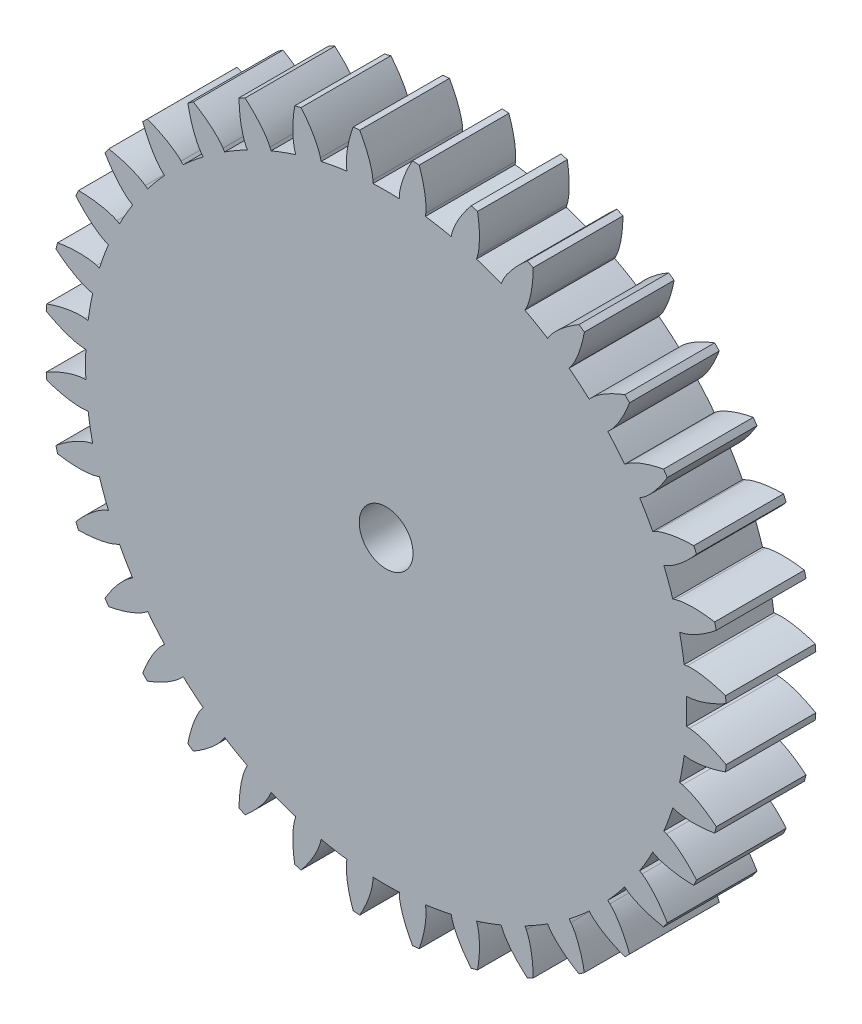
SolidWorks part; units mm, degrees
ref_plane "前视基准面" through (0, 0, 0) normal (0, 0, 1) x (1, 0, 0)
ref_plane "上视基准面" through (0, 0, 0) normal (0, 1, 0) x (1, 0, 0)
ref_plane "右视基准面" through (0, 0, 0) normal (1, 0, 0) x (0, 0, -1)
other "Configuration Table"
sketch "草图1" plane through (0, 0, 0) normal (0, 0, 1) x (1, 0, 0)
  line L0 (0, 0) -> (3, 0) construction
  line L1 (0, 0) -> (2.8978, 0.7765) construction
  line L2 (0, 0) -> (2.7305, 0.701)
  line L3 (2.8978, 0.7765) -> (2.8978, -0.7765) construction
  line L4 (0, 0) -> (2.7305, -0.701)
  circle A0 centre (0, 0) radius 4
  circle A1 centre (0, 0) radius 3 construction
  circle A2 centre (0, 0) radius 1.75
  circle A3 centre (0, 0) radius 2.8191 construction
  circle A4 centre (0, 0) radius 1.5
  spline S0 degree 4 poles (2.7305, 0.701) (2.7514, 0.7063) (2.8083, 0.7255) (2.9105, 0.779) (3.0627, 0.8875) (3.236, 1.0573) (3.4253, 1.3046) (3.6012, 1.6247) (3.742, 2.0003) (3.8364, 2.4221) (3.8779, 2.852) (3.8707, 3.2837) (3.8157, 3.7334) (3.69, 4.2802) (3.4574, 4.9086) (3.0836, 5.5918) (2.5556, 6.2772) (1.9356, 6.8796) (1.2391, 7.3923) (0.4849, 7.8122) (-0.3175, 8.1368) (-1.1468, 8.3674) (-2.0054, 8.5023) (-2.7502, 8.5427) (-3.4127, 8.5171) (-3.8849, 8.4708) (-4.3024, 8.4076) (-4.5772, 8.3558) (-4.9624, 8.2714) (-5.2496, 8.1908) (-5.5362, 8.1071) (-5.6783, 8.056) (-5.7704, 8.0254) knots 0 0 0 0 0 0.005604 0.015718 0.02996 0.048734 0.068727 0.096889 0.125051 0.153212 0.181374 0.209535 0.237696 0.271429 0.327752 0.384075 0.440398 0.496721 0.553044 0.609367 0.66569 0.722013 0.778336 0.834659 0.86282 0.890982 0.909091 0.931818 0.954545 0.977273 1 1 1 1 1 construction
  spline S1 degree 4 poles (2.7305, 0.701) (2.7514, 0.7063) (2.8083, 0.7255) (2.9105, 0.779) (3.0627, 0.8875) (3.236, 1.0573) (3.4253, 1.3046) (3.6012, 1.6247) (3.742, 2.0003) (3.8364, 2.4221) (3.8779, 2.852) (3.8707, 3.2837) (3.8157, 3.7334) (3.69, 4.2802) (3.4574, 4.9086) (3.0836, 5.5918) (2.5556, 6.2772) (1.9356, 6.8796) (1.2391, 7.3923) (0.4849, 7.8122) (-0.3175, 8.1368) (-1.1468, 8.3674) (-2.0054, 8.5023) (-2.7502, 8.5427) (-3.4127, 8.5171) (-3.8849, 8.4708) (-4.2047, 8.4224) (-4.3632, 8.395) (-4.4251, 8.3835) knots 0 0 0 0 0 0.005604 0.015718 0.02996 0.048734 0.068727 0.096889 0.125051 0.153212 0.181374 0.209535 0.237696 0.271429 0.327752 0.384075 0.440398 0.496721 0.553044 0.609367 0.66569 0.722013 0.778336 0.834659 0.86282 0.890982 0.909091 0.909091 0.909091 0.909091 0.909091
  spline S2 degree 4 poles (2.7305, -0.701) (2.7514, -0.7063) (2.8083, -0.7255) (2.9105, -0.779) (3.0627, -0.8875) (3.236, -1.0573) (3.4253, -1.3046) (3.6012, -1.6247) (3.742, -2.0003) (3.8364, -2.4221) (3.8779, -2.852) (3.8707, -3.2837) (3.8157, -3.7334) (3.69, -4.2802) (3.4574, -4.9086) (3.0836, -5.5918) (2.5556, -6.2772) (1.9356, -6.8796) (1.2391, -7.3923) (0.4849, -7.8122) (-0.3175, -8.1368) (-1.1468, -8.3674) (-2.0054, -8.5023) (-2.7502, -8.5427) (-3.4127, -8.5171) (-3.8849, -8.4708) (-4.3024, -8.4076) (-4.5772, -8.3558) (-4.9624, -8.2714) (-5.2496, -8.1908) (-5.5362, -8.1071) (-5.6783, -8.056) (-5.7704, -8.0254) knots 0 0 0 0 0 0.005604 0.015718 0.02996 0.048734 0.068727 0.096889 0.125051 0.153212 0.181374 0.209535 0.237696 0.271429 0.327752 0.384075 0.440398 0.496721 0.553044 0.609367 0.66569 0.722013 0.778336 0.834659 0.86282 0.890982 0.909091 0.931818 0.954545 0.977273 1 1 1 1 1 construction
  spline S3 degree 4 poles (2.7305, -0.701) (2.7514, -0.7063) (2.8083, -0.7255) (2.9105, -0.779) (3.0627, -0.8875) (3.236, -1.0573) (3.4253, -1.3046) (3.6012, -1.6247) (3.742, -2.0003) (3.8364, -2.4221) (3.8779, -2.852) (3.8707, -3.2837) (3.8157, -3.7334) (3.69, -4.2802) (3.4574, -4.9086) (3.0836, -5.5918) (2.5556, -6.2772) (1.9356, -6.8796) (1.2391, -7.3923) (0.4849, -7.8122) (-0.3175, -8.1368) (-1.1468, -8.3674) (-2.0054, -8.5023) (-2.7502, -8.5427) (-3.4127, -8.5171) (-3.8849, -8.4708) (-4.2047, -8.4224) (-4.3632, -8.395) (-4.4251, -8.3835) knots 0 0 0 0 0 0.005604 0.015718 0.02996 0.048734 0.068727 0.096889 0.125051 0.153212 0.181374 0.209535 0.237696 0.271429 0.327752 0.384075 0.440398 0.496721 0.553044 0.609367 0.66569 0.722013 0.778336 0.834659 0.86282 0.890982 0.909091 0.909091 0.909091 0.909091 0.909091
  point P15 (2.8978, 0)
  dimension "齿顶圆直径" = 8
  dimension "分度圆直径" = 6
  dimension "齿根圆直径" = 3.5
  dimension "基圆直径" = 5.6382
  dimension "内孔直径" = 3
  dimension "渐近线镜像线夹角" = 15
extrude "凸台-拉伸1" add sketch "草图1" along normal blind 5 contours A0 | A4
extrude "切除-拉伸1" cut sketch "草图1<3>" along normal through all contours A2 S3 A0 S1 region at (3.0753, 0, 0)
sketch "草图1<3>" plane through (0, 0, 0) normal (0, 0, 1) x (1, 0, 0) same geometry as "草图1"
pattern_circular "阵列(圆周)1" count 6 every 60 about axis through (0, 0, 5) along (0, 0, 1) of "切除-拉伸1"
sketch "草图2" plane through (0, 0, 5) normal (0, 0, 1) x (1, 0, 0)
  line L0 (0, 0) -> (18, 0) construction
  line L1 (0, 0) -> (16.8984, 0.7378)
  line L2 (0, 0) -> (16.8984, -0.7378)
  line L3 (16.8984, 0.7378) -> (16.8984, -0.7378) construction
  circle A0 centre (0, 0) radius 18 construction
  circle A1 centre (0, 0) radius 16.9145 construction
  circle A2 centre (0, 0) radius 16.75
  circle A3 centre (0, 0) radius 19
  circle A4 centre (0, 0) radius 1.5
  spline S0 degree 4 poles (16.8984, -0.7378) (16.9305, -0.7392) (16.9946, -0.744) (17.1222, -0.7613) (17.3623, -0.8094) (17.6792, -0.8979) (18.2656, -1.1114) (19.1537, -1.5549) (20.2605, -2.3067) (21.6402, -3.5683) (23.0181, -5.2717) (24.2472, -7.341) (25.2511, -9.7319) (25.9514, -12.2271) (26.3654, -14.7846) (26.5168, -17.4986) (26.353, -20.8608) (25.6449, -24.8182) (24.1592, -29.2488) (21.7683, -33.856) (18.7413, -38.0696) (15.6205, -41.3641) (12.6641, -43.8837) (10.0391, -45.7726) (7.8519, -47.1548) (5.0217, -48.719) (2.0772, -50.063) (-0.9572, -51.1847) (-4.6856, -52.2642) (-7.5306, -52.8747) (-10.0928, -53.2637) (-12.1778, -53.4743) (-13.1552, -53.5512) (-14.0988, -53.6122) (-15.0049, -53.6515) (-15.8075, -53.6779) (-16.967, -53.687) (-17.5735, -53.6824) (-18.4532, -53.6655) (-19.1605, -53.6386) (-19.9868, -53.6008) (-20.868, -53.5426) (-21.9266, -53.4557) (-22.9527, -53.3491) (-23.9974, -53.2227) (-24.7654, -53.1134) (-25.2852, -53.034) (-25.541, -52.9927) knots 0 0 0 0 0 0.001401 0.002802 0.005604 0.010661 0.015718 0.02996 0.048734 0.068727 0.096889 0.125051 0.153212 0.181374 0.209535 0.237696 0.271429 0.327752 0.384075 0.440398 0.496721 0.553044 0.581206 0.609367 0.637529 0.66569 0.722013 0.750174 0.778336 0.834659 0.84874 0.86282 0.869861 0.876901 0.890982 0.900036 0.909091 0.920455 0.926136 0.931818 0.943182 0.954545 0.965909 0.977273 0.988636 1 1 1 1 1 construction
  spline S1 degree 4 poles (16.8984, -0.7378) (16.9305, -0.7392) (16.9946, -0.744) (17.1222, -0.7613) (17.3623, -0.8094) (17.6792, -0.8979) (18.2656, -1.1114) (19.1537, -1.5549) (20.2605, -2.3067) (21.6402, -3.5683) (23.0181, -5.2717) (24.2472, -7.341) (25.2511, -9.7319) (25.9514, -12.2271) (26.3654, -14.7846) (26.5168, -17.4986) (26.353, -20.8608) (25.6449, -24.8182) (24.1592, -29.2488) (21.7683, -33.856) (18.7413, -38.0696) (15.6205, -41.3641) (12.6641, -43.8837) (10.0391, -45.7726) (7.8519, -47.1548) (5.0217, -48.719) (2.0772, -50.063) (-0.9572, -51.1847) (-4.6856, -52.2642) (-7.5306, -52.8747) (-10.0928, -53.2637) (-12.1778, -53.4743) (-13.1552, -53.5512) (-14.0988, -53.6122) (-15.0049, -53.6515) (-15.8075, -53.6779) (-16.6645, -53.6846) (-17.0423, -53.6846) (-17.2312, -53.6835) knots 0 0 0 0 0 0.001401 0.002802 0.005604 0.010661 0.015718 0.02996 0.048734 0.068727 0.096889 0.125051 0.153212 0.181374 0.209535 0.237696 0.271429 0.327752 0.384075 0.440398 0.496721 0.553044 0.581206 0.609367 0.637529 0.66569 0.722013 0.750174 0.778336 0.834659 0.84874 0.86282 0.869861 0.876901 0.890982 0.900036 0.909091 0.909091 0.909091 0.909091 0.909091
  spline S2 degree 4 poles (16.8984, 0.7378) (16.9305, 0.7392) (16.9946, 0.744) (17.1222, 0.7613) (17.3623, 0.8094) (17.6792, 0.8979) (18.2656, 1.1114) (19.1537, 1.5549) (20.2605, 2.3067) (21.6402, 3.5683) (23.0181, 5.2717) (24.2472, 7.341) (25.2511, 9.7319) (25.9514, 12.2271) (26.3654, 14.7846) (26.5168, 17.4986) (26.353, 20.8608) (25.6449, 24.8182) (24.1592, 29.2488) (21.7683, 33.856) (18.7413, 38.0696) (15.6205, 41.3641) (12.6641, 43.8837) (10.0391, 45.7726) (7.8519, 47.1548) (5.0217, 48.719) (2.0772, 50.063) (-0.9572, 51.1847) (-4.6856, 52.2642) (-7.5306, 52.8747) (-10.0928, 53.2637) (-12.1778, 53.4743) (-13.1552, 53.5512) (-14.0988, 53.6122) (-15.0049, 53.6515) (-15.8075, 53.6779) (-16.967, 53.687) (-17.5735, 53.6824) (-18.4532, 53.6655) (-19.1605, 53.6386) (-19.9868, 53.6008) (-20.868, 53.5426) (-21.9266, 53.4557) (-22.9527, 53.3491) (-23.9974, 53.2227) (-24.7654, 53.1134) (-25.2852, 53.034) (-25.541, 52.9927) knots 0 0 0 0 0 0.001401 0.002802 0.005604 0.010661 0.015718 0.02996 0.048734 0.068727 0.096889 0.125051 0.153212 0.181374 0.209535 0.237696 0.271429 0.327752 0.384075 0.440398 0.496721 0.553044 0.581206 0.609367 0.637529 0.66569 0.722013 0.750174 0.778336 0.834659 0.84874 0.86282 0.869861 0.876901 0.890982 0.900036 0.909091 0.920455 0.926136 0.931818 0.943182 0.954545 0.965909 0.977273 0.988636 1 1 1 1 1 construction
  spline S3 degree 4 poles (16.8984, 0.7378) (16.9305, 0.7392) (16.9946, 0.744) (17.1222, 0.7613) (17.3623, 0.8094) (17.6792, 0.8979) (18.2656, 1.1114) (19.1537, 1.5549) (20.2605, 2.3067) (21.6402, 3.5683) (23.0181, 5.2717) (24.2472, 7.341) (25.2511, 9.7319) (25.9514, 12.2271) (26.3654, 14.7846) (26.5168, 17.4986) (26.353, 20.8608) (25.6449, 24.8182) (24.1592, 29.2488) (21.7683, 33.856) (18.7413, 38.0696) (15.6205, 41.3641) (12.6641, 43.8837) (10.0391, 45.7726) (7.8519, 47.1548) (5.0217, 48.719) (2.0772, 50.063) (-0.9572, 51.1847) (-4.6856, 52.2642) (-7.5306, 52.8747) (-10.0928, 53.2637) (-12.1778, 53.4743) (-13.1552, 53.5512) (-14.0988, 53.6122) (-15.0049, 53.6515) (-15.8075, 53.6779) (-16.6645, 53.6846) (-17.0423, 53.6846) (-17.2312, 53.6835) knots 0 0 0 0 0 0.001401 0.002802 0.005604 0.010661 0.015718 0.02996 0.048734 0.068727 0.096889 0.125051 0.153212 0.181374 0.209535 0.237696 0.271429 0.327752 0.384075 0.440398 0.496721 0.553044 0.581206 0.609367 0.637529 0.66569 0.722013 0.750174 0.778336 0.834659 0.84874 0.86282 0.869861 0.876901 0.890982 0.900036 0.909091 0.909091 0.909091 0.909091 0.909091
  point P16 (16.8984, 0)
  dimension "内孔直径" = 3
  dimension "分度圆直径" = 36
  dimension "齿顶圆直径" = 38
  dimension "基圆直径" = 33.8289
  dimension "齿根圆直径" = 33.5
  dimension "渐开线镜像线夹角" = 2.5
extrude "凸台-拉伸2" add sketch "草图2" along normal blind 5 contours A3 | A4
extrude "切除-拉伸3" cut sketch "草图2<3>" along normal through all contours S3 L1 A2 L2 S1 A3 region at (18.0071, 0, 5)
sketch "草图2<3>" plane through (0, 0, 5) normal (0, 0, 1) x (1, 0, 0) same geometry as "草图2"
pattern_circular "阵列(圆周)2" count 36 over 360 about axis through (0, 0, 10) along (0, 0, 1) of "切除-拉伸3"
equation "\"m\" = 1'模数"
equation "\"z\" = 6'齿数"
equation "\"a\"= 20度'压力角"
equation "\"d\"= \"m\" * \"z\"'分度圆直径"
equation "\"da\"= ( \"z\" + 2 ) * \"m\"'齿顶圆直径"
equation "\"df\"= ( \"z\" - 2.5 ) * \"m\"'齿根圆直径"
equation "\"s\"= 0.5 * PI * \"m\"'分度圆齿厚"
equation "\"r\"= 0.38 * \"m\"'齿根圆角"
equation "\"B\"= 0.3 * \"d\"'齿厚"
equation "\"db\"= \"m\" * \"z\" * cos ( \"a\" )'基圆直径"
equation "\"rb\"= \"db\" / 2'基圆半径"
equation "\"齿顶圆直径@草图1\"= \"da\""
equation "\"分度圆直径@草图1\"= \"d\""
equation "\"齿根圆直径@草图1\"= \"df\""
equation "\"基圆直径@草图1\"= \"db\""
equation "\"渐近线镜像线夹角@草图1\"= 360 / 4 / \"z\""
equation "\"h\" = 5'齿轮厚度"
equation "\"ir\" = 3'内孔直径"
equation "\"内孔直径@草图1\"= \"ir\""
equation "\"齿轮厚@凸台-拉伸1\"= \"h\""
equation "\"齿轮夹角@阵列(圆周)1\"= 360 / \"z\""
equation "\"齿数@阵列(圆周)1\"= \"z\""
equation "\"m1\" = 1'模数"
equation "\"z1\" = 36'齿数"
equation "\"a1\"= 20度'压力角"
equation "\"d1\"= \"m1\" * \"z1\"'分度圆直径"
equation "\"da1\"= ( \"z1\" + 2 ) * \"m1\"'齿顶圆直径"
equation "\"df1\"= ( \"z1\" - 2.5 ) * \"m1\"'齿根圆直径"
equation "\"s1\"= 0.5 * PI * \"m1\"'分度圆齿厚"
equation "\"r1\"= 0.38 * \"m1\"'齿根圆角"
equation "\"B1\"= 0.3 * \"d1\"'齿厚"
equation "\"db1\"= \"m1\" * \"z1\" * cos ( \"a1\" )'基圆直径"
equation "\"rb1\"= \"db1\" / 2'基圆半径"
equation "\"分度圆直径@草图2\"= \"d1\""
equation "\"齿顶圆直径@草图2\"= \"da1\""
equation "\"基圆直径@草图2\"= \"db1\""
equation "\"齿根圆直径@草图2\"= \"df1\""
equation "\"渐开线镜像线夹角@草图2\"= 360 / 4 / \"z1\""
equation "\"内孔直径@草图2\"= \"ir\""
equation "\"二层齿轮厚@凸台-拉伸2\" = \"h1\""
equation "\"h1\"= 5'齿轮厚度"
equation "\"二层齿数@阵列(圆周)2\"= \"z1\""
